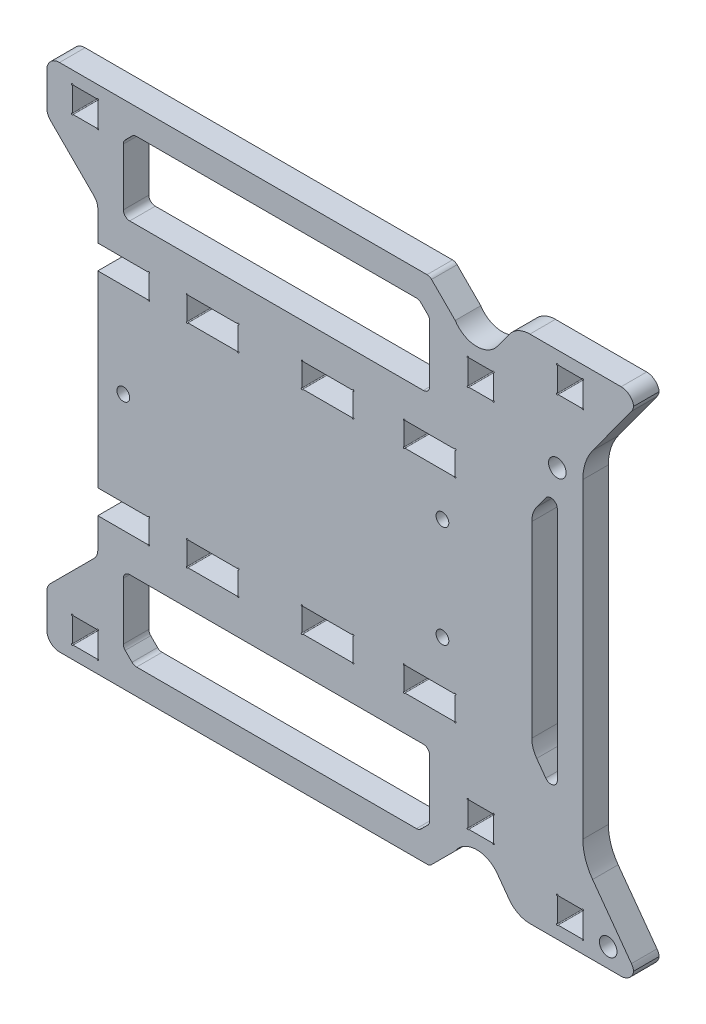
SolidWorks part; units mm, degrees
ref_plane "Front Plane" through (0, 0, 0) normal (0, 0, 1) x (1, 0, 0)
ref_plane "Top Plane" through (0, 0, 0) normal (0, 1, 0) x (1, 0, 0)
ref_plane "Right Plane" through (0, 0, 0) normal (1, 0, 0) x (0, 0, -1)
sketch "Sketch1" plane through (0, 0, 0) normal (0, 0, 1) x (1, 0, 0)
  line L0 (83.672, 0) -> (-43.8164, 0) construction
  line L1 (10.525, 38.1) -> (10.525, -38.1) construction
  line L2 (-27.575, 38.1) -> (48.625, 38.1)
  line L3 (99.425, -63.5) -> (99.425, -60.325)
  line L4 (99.425, -60.325) -> (74.025, -25.4)
  line L5 (-27.575, -63.5) -> (48.625, -63.5)
  line L6 (-27.575, 38.1) -> (-27.575, 54.5197)
  line L7 (48.625, 38.1) -> (48.625, 54.5197)
  line L8 (-24.9447, 57.15) -> (45.9947, 57.15)
  line L9 (-27.575, 63.5) -> (48.625, 63.5)
  line L10 (-33.925, 57.15) -> (-33.925, -57.15)
  line L11 (-27.575, 63.5) -> (-33.925, 57.15)
  line L12 (-24.9447, 57.15) -> (-27.575, 54.5197)
  line L13 (99.425, 63.5) -> (99.425, 60.325)
  line L14 (-23.0849, 59.0099) -> (-29.4349, 52.6599) construction
  line L15 (99.425, 60.325) -> (74.025, 25.4)
  line L16 (74.025, 25.4) -> (74.025, -25.4)
  line L17 (48.625, -38.1) -> (48.625, -54.5197)
  line L18 (-27.575, -38.1) -> (48.625, -38.1)
  line L19 (-24.9447, -57.15) -> (45.9947, -57.15)
  line L20 (-24.9447, -57.15) -> (-27.575, -54.5197)
  line L21 (-27.575, -38.1) -> (-27.575, -54.5197)
  line L22 (-27.575, -63.5) -> (-33.925, -57.15)
  line L23 (48.625, -63.5) -> (54.975, -57.15)
  line L24 (48.625, 63.5) -> (54.975, 57.15)
  line L25 (70.3271, -63.5) -> (99.425, -63.5)
  line L26 (45.9947, 57.15) -> (48.625, 54.5197)
  line L27 (45.9947, -57.15) -> (48.625, -54.5197)
  line L28 (70.3271, 63.5) -> (65.7089, 57.15)
  line L29 (70.3271, 63.5) -> (99.425, 63.5)
  line L30 (78.8831, 75.2646) -> (53.4831, 40.3396) construction
  line L31 (54.975, -42.3909) -> (54.975, -57.15)
  line L32 (70.3271, -63.5) -> (65.7089, -57.15)
  line L34 (48.625, -63.5) -> (54.975, -57.15)
  line L35 (65.7089, 57.15) -> (54.975, 42.3909)
  line L36 (54.975, 42.3909) -> (54.975, 57.15)
  line L37 (65.7089, -57.15) -> (54.975, -42.3909)
  point P7 (-27.575, 0)
  point P21 (74.025, 0)
  point P22 (-33.925, 0)
  dimension "D1" = 25.4
  dimension "D2" = 76.2
  dimension "D3" = 127
  dimension "D4" = 6.35
  dimension "D7" = 3.175
  dimension "D8" = 25.4
  dimension "D9" = 25.4
  dimension "D6" = 6.35
extrude "Boss-Extrude1" add sketch "Sketch1" along normal blind 6.35 contours L23 L32 L25 L3 L4 L16 L15 L13 L29 L28 L24 L9 L11 L10 L22 L5 L8 L26 L7 L2 L6 L12 L27 L19 L20 L21 L18 L17 region at (27.1557, 0, 0)
fillet "Fillet1" radius 6.35 4 edges at (70.3271, 63.5, 3.175) (70.3271, -63.5, 3.175) (54.975, -42.3909, 3.175) (54.975, 42.3909, 3.175)
fillet "Fillet3" radius 3.175 4 edges at (99.425, 63.5, 3.175) (99.425, 60.325, 3.175) (99.425, -60.325, 3.175) (99.425, -63.5, 3.175)
fillet "Fillet4" radius 6.35 2 edges at (74.025, -25.4, 3.175) (74.025, 25.4, 3.175)
fillet "Fillet7" radius 1.5875 4 edges at (-27.575, -38.1, 3.175) (48.625, -38.1, 3.175) (48.625, 38.1, 3.175) (-27.575, 38.1, 3.175)
fillet "Fillet8" radius 1.5875 2 edges at (48.625, -63.5, 3.175) (48.625, 63.5, 3.175)
fillet "Fillet9" radius 1.5875 8 edges at (-27.575, 54.5197, 3.175) (-24.9447, 57.15, 3.175) (-27.575, -54.5197, 3.175) (-24.9447, -57.15, 3.175) (45.9947, -57.15, 3.175) (48.625, -54.5197, 3.175) (48.625, 54.5197, 3.175) (45.9947, 57.15, 3.175)
sketch "Sketch2" plane through (0, 0, 6.35) normal (0, 0, 1) x (1, 0, 0)
  line L0 (-33.925, 0) -> (74.025, 0) construction
  line L1 (-33.925, 57.15) -> (-33.925, -57.15) construction
  line L2 (74.025, 23.3351) -> (74.025, -23.3351) construction
  line L3 (48.625, 39.6875) -> (48.625, 53.8622) construction
  line L4 (58.3484, 50.8) -> (64.3016, 50.8)
  line L5 (58.15, 50.6016) -> (58.15, 44.6484)
  line L6 (58.3484, 44.45) -> (64.3016, 44.45)
  line L7 (64.5, 50.6016) -> (64.5, 44.6484)
  line L8 (64.5, -50.6016) -> (64.5, -44.6484)
  line L9 (58.3484, -50.8) -> (64.3016, -50.8)
  line L10 (58.15, -50.6016) -> (58.15, -44.6484)
  line L11 (58.3484, -44.45) -> (64.3016, -44.45)
  arc A0 (58.3484, 50.8) -> (58.15, 50.6016) centre (58.15, 50.8) ccw
  arc A1 (64.5, 50.6016) -> (64.3016, 50.8) centre (64.5, 50.8) ccw
  arc A2 (64.3016, 44.45) -> (64.5, 44.6484) centre (64.5, 44.45) ccw
  arc A3 (58.15, 44.6484) -> (58.3484, 44.45) centre (58.15, 44.45) ccw
  arc A4 (64.3016, -44.45) -> (64.5, -44.6484) centre (64.5, -44.45) cw
  arc A5 (64.5, -50.6016) -> (64.3016, -50.8) centre (64.5, -50.8) cw
  arc A6 (58.3484, -50.8) -> (58.15, -50.6016) centre (58.15, -50.8) cw
  arc A7 (58.15, -44.6484) -> (58.3484, -44.45) centre (58.15, -44.45) cw
  point P10 (48.625, 46.7748)
  dimension "D5" = 0.3969
  dimension "D6" = 0.3969
  dimension "D7" = 0.3969
  dimension "D8" = 0.3969
  dimension "D1" = 6.35
  dimension "D2" = 6.35
  dimension "D3" = 50.8
  dimension "D4" = 9.525
extrude "Cut-Extrude1" cut sketch "Sketch2" against normal through all
sketch "Sketch5" plane through (0, 0, 6.35) normal (0, 0, 1) x (1, 0, 0)
  line L0 (-33.925, 29.3675) -> (74.025, 29.3675) construction
  line L1 (-33.925, 57.15) -> (-33.925, -57.15) construction
  line L2 (74.025, 23.3351) -> (74.025, -23.3351) construction
  line L3 (-25.9875, 38.1) -> (47.0375, 38.1) construction
  line L4 (-33.925, 23.3731) -> (74.025, 23.3731) construction
  line L5 (-33.925, 0) -> (74.025, 0) construction
  line L6 (-11.5016, 29.3675) -> (0.8016, 29.3675)
  line L7 (-11.7, 29.169) -> (-11.7, 23.5715)
  line L8 (-11.5016, 23.3731) -> (0.8016, 23.3731)
  line L9 (1, 29.169) -> (1, 23.5715)
  line L10 (42.4734, 29.3675) -> (54.7766, 29.3675)
  line L11 (42.275, 29.169) -> (42.275, 23.5715)
  line L12 (42.4734, 23.3731) -> (54.7766, 23.3731)
  line L13 (54.975, 29.169) -> (54.975, 23.5715)
  line L14 (29.3766, 29.3675) -> (17.0734, 29.3675)
  line L15 (29.575, 29.169) -> (29.575, 23.5715)
  line L16 (29.3766, 23.3731) -> (17.0734, 23.3731)
  line L17 (16.875, 29.169) -> (16.875, 23.5715)
  line L18 (-21.4234, 29.3675) -> (-33.925, 29.3675)
  line L19 (-21.225, 29.169) -> (-21.225, 23.5715)
  line L20 (-21.4234, 23.3731) -> (-33.925, 23.3731)
  line L21 (-33.925, 29.3675) -> (-33.925, 23.3731)
  line L22 (-33.925, -29.3675) -> (-33.925, -23.3731)
  line L23 (-21.4234, -23.3731) -> (-33.925, -23.3731)
  line L24 (-21.225, -29.169) -> (-21.225, -23.5715)
  line L25 (-21.4234, -29.3675) -> (-33.925, -29.3675)
  line L26 (16.875, -29.169) -> (16.875, -23.5715)
  line L27 (29.3766, -23.3731) -> (17.0734, -23.3731)
  line L28 (29.575, -29.169) -> (29.575, -23.5715)
  line L29 (29.3766, -29.3675) -> (17.0734, -29.3675)
  line L30 (54.975, -29.169) -> (54.975, -23.5715)
  line L31 (42.4734, -23.3731) -> (54.7766, -23.3731)
  line L32 (42.275, -29.169) -> (42.275, -23.5715)
  line L33 (42.4734, -29.3675) -> (54.7766, -29.3675)
  line L34 (1, -29.169) -> (1, -23.5715)
  line L35 (-11.5016, -23.3731) -> (0.8016, -23.3731)
  line L36 (-11.7, -29.169) -> (-11.7, -23.5715)
  line L37 (-11.5016, -29.3675) -> (0.8016, -29.3675)
  line L38 (-33.925, 26.3703) -> (54.975, 26.3703) construction
  arc A0 (-21.225, 29.169) -> (-21.4234, 29.3675) centre (-21.225, 29.3675) ccw
  arc A1 (-11.5016, 29.3675) -> (-11.7, 29.169) centre (-11.7, 29.3675) ccw
  arc A2 (1, 29.169) -> (0.8016, 29.3675) centre (1, 29.3675) ccw
  arc A3 (29.575, 29.169) -> (29.3766, 29.3675) centre (29.575, 29.3675) ccw
  arc A4 (17.0734, 29.3675) -> (16.875, 29.169) centre (16.875, 29.3675) ccw
  arc A5 (54.975, 29.169) -> (54.7766, 29.3675) centre (54.975, 29.3675) ccw
  arc A6 (42.4734, 29.3675) -> (42.275, 29.169) centre (42.275, 29.3675) ccw
  arc A7 (17.0734, 23.3731) -> (16.875, 23.5715) centre (16.875, 23.3731) cw
  arc A8 (29.575, 23.5715) -> (29.3766, 23.3731) centre (29.575, 23.3731) cw
  arc A9 (42.4734, 23.3731) -> (42.275, 23.5715) centre (42.275, 23.3731) cw
  arc A10 (54.975, 23.5715) -> (54.7766, 23.3731) centre (54.975, 23.3731) cw
  arc A11 (1, 23.5715) -> (0.8016, 23.3731) centre (1, 23.3731) cw
  arc A12 (-11.5016, 23.3731) -> (-11.7, 23.5715) centre (-11.7, 23.3731) cw
  arc A13 (-21.225, 23.5715) -> (-21.4234, 23.3731) centre (-21.225, 23.3731) cw
  arc A14 (-21.225, -23.5715) -> (-21.4234, -23.3731) centre (-21.225, -23.3731) ccw
  arc A15 (-11.5016, -23.3731) -> (-11.7, -23.5715) centre (-11.7, -23.3731) ccw
  arc A16 (1, -23.5715) -> (0.8016, -23.3731) centre (1, -23.3731) ccw
  arc A17 (54.975, -23.5715) -> (54.7766, -23.3731) centre (54.975, -23.3731) ccw
  arc A18 (42.4734, -23.3731) -> (42.275, -23.5715) centre (42.275, -23.3731) ccw
  arc A19 (29.575, -23.5715) -> (29.3766, -23.3731) centre (29.575, -23.3731) ccw
  arc A20 (17.0734, -23.3731) -> (16.875, -23.5715) centre (16.875, -23.3731) ccw
  arc A21 (42.4734, -29.3675) -> (42.275, -29.169) centre (42.275, -29.3675) cw
  arc A22 (54.975, -29.169) -> (54.7766, -29.3675) centre (54.975, -29.3675) cw
  arc A23 (17.0734, -29.3675) -> (16.875, -29.169) centre (16.875, -29.3675) cw
  arc A24 (29.575, -29.169) -> (29.3766, -29.3675) centre (29.575, -29.3675) cw
  arc A25 (1, -29.169) -> (0.8016, -29.3675) centre (1, -29.3675) cw
  arc A26 (-11.5016, -29.3675) -> (-11.7, -29.169) centre (-11.7, -29.3675) cw
  arc A27 (-21.225, -29.169) -> (-21.4234, -29.3675) centre (-21.225, -29.3675) cw
  dimension "D11" = 0.3969
  dimension "D12" = 0.3969
  dimension "D13" = 0.3969
  dimension "D14" = 0.3969
  dimension "D15" = 0.3969
  dimension "D16" = 0.3969
  dimension "D17" = 0.3969
  dimension "D1" = 8.7325
  dimension "D3" = 12.7
  dimension "D4" = 12.7
  dimension "D5" = 41.275
  dimension "D6" = 34.925
  dimension "D7" = 12.7
  dimension "D8" = 12.7
  dimension "D9" = 50.8
  dimension "D10" = 0
  dimension "D2" = 5.9944
extrude "Cut-Extrude4" cut sketch "Sketch5" against normal through all
sketch "Sketch6" plane through (0, 0, 6.35) normal (0, 0, 1) x (1, 0, 0)
  line L0 (80.375, 34.1312) -> (80.375, -34.1312)
  line L1 (98.8177, 59.49) -> (75.2395, 27.07) construction
  line L2 (98.8177, -59.49) -> (75.2395, -27.07) construction
  line L3 (74.025, 23.3351) -> (74.025, -23.3351) construction
  line L4 (86.725, 34.1312) -> (86.725, -34.1312)
  line L5 (86.725, 34.1312) -> (86.725, 42.8625)
  line L6 (86.725, 42.8625) -> (80.375, 34.1312)
  line L7 (86.725, -34.1312) -> (86.725, -42.8625)
  line L8 (86.725, -42.8625) -> (80.375, -34.1312)
  dimension "D1" = 6.35
  dimension "D2" = 6.35
extrude "Boss-Extrude2" add sketch "Sketch6" against normal blind 6.35
fillet "Fillet10" radius 1.5875 2 edges at (80.375, -34.1312, 3.175) (80.375, 34.1312, 3.175)
fillet "Fillet11" radius 12.7 2 edges at (86.725, 42.8625, 3.175) (86.725, -42.8625, 3.175)
hole_wizard "11/64 (0.17188) Diameter Hole1" positions "Sketch8" profile "Sketch7" hole size "11/64" standard "ANSI Inch" end condition through all
sketch "Sketch8" plane through (0, 0, 6.35) normal (0, 0, 1) x (1, 0, 0)
  line L1 (-33.925, -29.3675) -> (-33.925, -57.15) construction
  line L2 (73.5606, 63.5) -> (96.25, 63.5) construction
  point P0 (80.375, 38.1)
  dimension "D1" = 25.4
  dimension "D2" = 114.3
sketch "Sketch7" plane through (80.375, 38.1, 6.35) normal (1, 0, 0) x (0, -1, 0)
  line L0 (0, 0) -> (0, 6.35)
  line L1 (0, 6.35) -> (2.1829, 6.35)
  line L2 (2.1829, 6.35) -> (2.1829, 0)
  line L5 (2.1829, 0) -> (0, 0)
  line L11 (0, -6.35) -> (0, 107.95) construction
  dimension "Thru Hole Dia." = 4.3658
  dimension "Thru Hole Depth" = 6.35
sketch "Sketch10" plane through (0, 0, 6.35) normal (0, 0, 1) x (1, 0, 0)
  line L0 (51.8, 63.5) -> (51.8, -63.5) construction
  line L1 (-27.575, 63.5) -> (47.9674, 63.5) construction
  line L2 (-27.575, -63.5) -> (47.9674, -63.5) construction
  line L3 (23.225, 29.3675) -> (23.225, -29.3675) construction
  line L4 (29.3766, 29.3675) -> (17.0734, 29.3675) construction
  line L5 (17.0734, -29.3675) -> (29.3766, -29.3675) construction
  line L6 (-27.575, 63.5) -> (-27.575, -63.5) construction
  line L7 (-33.925, 0) -> (74.025, 0) construction
  line L8 (-33.925, 23.3731) -> (-33.925, -23.3731) construction
  line L9 (74.025, 23.3351) -> (74.025, -23.3351) construction
  circle A0 centre (51.8, 12.7) radius 1.5875
  circle A1 centre (51.8, -12.7) radius 1.5875
  circle A2 centre (-27.575, 0) radius 1.5875
  dimension "D3" = 3.175
  dimension "D5" = 79.375
  dimension "D1" = 28.575
  dimension "D2" = 79.375
  dimension "D4" = 12.7
extrude "Cut-Extrude6" cut sketch "Sketch10" against normal through all
sketch "Sketch11" plane through (0, 0, 6.35) normal (0, 0, 1) x (1, 0, 0)
  line L0 (-62.0481, -60.325) -> (124.8486, -60.325) construction
  line L1 (-27.575, -63.5) -> (47.9674, -63.5) construction
  line L2 (-27.575, -63.5) -> (-33.925, -57.15)
  line L3 (-33.925, -57.15) -> (-33.925, -50.8)
  line L4 (-33.925, -50.8) -> (-33.925, -38.1)
  line L5 (-46.625, -50.8) -> (-46.625, -63.5)
  line L6 (-46.625, -63.5) -> (-27.575, -63.5)
  line L7 (-46.625, -50.8) -> (-33.925, -38.1)
  line L8 (-33.925, -29.3675) -> (-33.925, -57.15) construction
  line L9 (-46.625, 63.5) -> (-27.575, 63.5)
  line L10 (-33.925, 0) -> (74.025, 0) construction
  line L11 (-46.625, 50.8) -> (-46.625, 63.5)
  line L12 (-33.925, 23.3731) -> (-33.925, -23.3731) construction
  line L13 (74.025, 23.3351) -> (74.025, -23.3351) construction
  line L14 (-46.625, 50.8) -> (-33.925, 38.1)
  line L15 (-33.925, 57.15) -> (-33.925, 50.8)
  line L16 (-27.575, 63.5) -> (-33.925, 57.15)
  line L17 (-33.925, 50.8) -> (-33.925, 38.1)
  point P2 (10.1962, -63.5)
  dimension "D1" = 3.175
  dimension "D2" = 12.7
  dimension "D3" = 12.7
extrude "Boss-Extrude4" add sketch "Sketch11" against normal blind 6.35
sketch "Sketch12" plane through (0, 0, 6.35) normal (0, 0, 1) x (1, 0, 0)
  line L0 (73.5606, -63.5) -> (96.25, -63.5) construction
  line L1 (86.5266, -60.325) -> (80.5734, -60.325)
  line L2 (86.725, -60.1266) -> (86.725, -54.1734)
  line L3 (86.5266, -53.975) -> (80.5734, -53.975)
  line L4 (80.375, -60.1266) -> (80.375, -54.1734)
  line L5 (-33.925, -29.3675) -> (-33.925, -38.1) construction
  line L6 (-33.925, 0) -> (74.025, 0) construction
  line L7 (86.725, 60.1266) -> (86.725, 54.1734)
  line L8 (86.5266, 60.325) -> (80.5734, 60.325)
  line L9 (80.375, 60.1266) -> (80.375, 54.1734)
  line L10 (86.5266, 53.975) -> (80.5734, 53.975)
  line L11 (83.55, -60.325) -> (-33.7266, -60.325) construction
  line L12 (-34.1234, -60.325) -> (-54.5439, -60.325) construction
  line L13 (-34.1234, -60.325) -> (-40.0766, -60.325)
  line L14 (-33.925, -60.1266) -> (-33.925, -54.1734)
  line L15 (-34.1234, -53.975) -> (-40.0766, -53.975)
  line L16 (-40.275, -60.1266) -> (-40.275, -54.1734)
  line L17 (-34.1234, 60.325) -> (-40.0766, 60.325)
  line L18 (-33.925, 60.1266) -> (-33.925, 54.1734)
  line L19 (-40.275, 60.1266) -> (-40.275, 54.1734)
  line L20 (-34.1234, 53.975) -> (-40.0766, 53.975)
  arc A0 (-40.275, 60.1266) -> (-40.0766, 60.325) centre (-40.275, 60.325) cw
  arc A1 (80.5734, -53.975) -> (80.375, -54.1734) centre (80.375, -53.975) ccw
  arc A2 (86.725, -54.1734) -> (86.5266, -53.975) centre (86.725, -53.975) ccw
  arc A3 (80.375, -60.1266) -> (80.5734, -60.325) centre (80.375, -60.325) ccw
  arc A4 (86.5266, -60.325) -> (86.725, -60.1266) centre (86.725, -60.325) ccw
  arc A5 (86.5266, 60.325) -> (86.725, 60.1266) centre (86.725, 60.325) cw
  arc A6 (80.375, 60.1266) -> (80.5734, 60.325) centre (80.375, 60.325) cw
  arc A7 (80.5734, 53.975) -> (80.375, 54.1734) centre (80.375, 53.975) cw
  arc A8 (86.725, 54.1734) -> (86.5266, 53.975) centre (86.725, 53.975) cw
  arc A9 (-40.0766, -53.975) -> (-40.275, -54.1734) centre (-40.275, -53.975) ccw
  arc A10 (-33.925, -54.1734) -> (-34.1234, -53.975) centre (-33.925, -53.975) ccw
  arc A11 (-34.1234, -60.325) -> (-33.925, -60.1266) centre (-33.925, -60.325) ccw
  arc A12 (-40.275, -60.1266) -> (-40.0766, -60.325) centre (-40.275, -60.325) ccw
  arc A13 (-34.1234, 60.325) -> (-33.925, 60.1266) centre (-33.925, 60.325) cw
  arc A14 (-33.925, 54.1734) -> (-34.1234, 53.975) centre (-33.925, 53.975) cw
  arc A15 (-40.0766, 53.975) -> (-40.275, 54.1734) centre (-40.275, 53.975) cw
  point P4 (84.9053, -63.5)
  dimension "D5" = 0.3969
  dimension "D6" = 0.3969
  dimension "D7" = 0.3969
  dimension "D8" = 0.3969
  dimension "D12" = 0.3969
  dimension "D13" = 0.3969
  dimension "D14" = 0.3969
  dimension "D15" = 0.3969
  dimension "D1" = 6.35
  dimension "D2" = 6.35
  dimension "D3" = 3.175
  dimension "D4" = 114.3
  dimension "D9" = 6.35
  dimension "D10" = 6.35
  dimension "D11" = 120.65
extrude "Cut-Extrude7" cut sketch "Sketch12" against normal blind 6.35
fillet "Fillet12" radius 3.175 6 edges at (-46.625, 63.5, 3.175) (-46.625, 50.8, 3.175) (-33.925, 38.1, 3.175) (-46.625, -63.5, 3.175) (-46.625, -50.8, 3.175) (-33.925, -38.1, 3.175)
hole_wizard "11/64 (0.17188) Diameter Hole2" positions "Sketch14" profile "Sketch13" hole size "11/64" standard "ANSI Inch" end condition through all
sketch "Sketch14" plane through (0, 0, 0) normal (0, 0, -1) x (-1, 0, 0)
  line L0 (-73.5606, -63.5) -> (-96.25, -63.5) construction
  point P0 (-93.0328, -58.7375)
  dimension "D1" = 4.7625
  dimension "D2" = 6.35
sketch "Sketch13" plane through (93.0328, -58.7375, 0) normal (1, 0, 0) x (0, 1, 0)
  line L0 (0, 0) -> (0, 6.35)
  line L1 (0, 6.35) -> (2.1829, 6.35)
  line L2 (2.1829, 6.35) -> (2.1829, 0)
  line L5 (2.1829, 0) -> (0, 0)
  line L11 (0, -6.35) -> (0, 107.95) construction
  dimension "Thru Hole Dia." = 4.3658
  dimension "Thru Hole Depth" = 6.35
